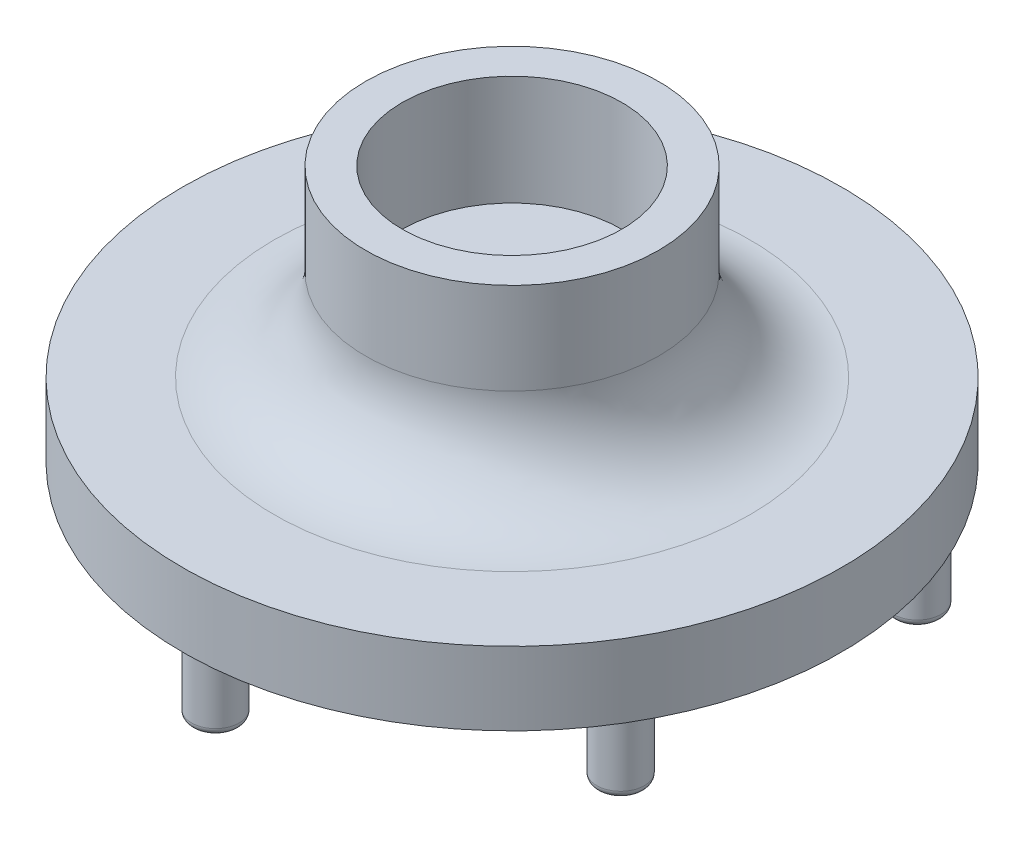
SolidWorks part; units mm, degrees
ref_plane "Front Plane" through (0, 0, 0) normal (0, 0, 1) x (1, 0, 0)
ref_plane "Top Plane" through (0, 0, 0) normal (0, 1, 0) x (1, 0, 0)
ref_plane "Right Plane" through (0, 0, 0) normal (1, 0, 0) x (0, 0, -1)
sketch "Sketch1" plane through (0, 0, 0) normal (0, 0, 1) x (1, 0, 0)
  line L0 (0, 0) -> (-30, 0)
  line L1 (-30, 0) -> (-30, 30)
  line L2 (-30, 30) -> (-50, 30)
  line L3 (-50, 30) -> (-50, 35)
  line L4 (-50, 35) -> (-90, 35)
  line L5 (-90, 35) -> (-90, 55)
  line L6 (-90, 55) -> (-40, 55)
  line L7 (-40, 55) -> (-40, 105)
  line L8 (-40, 105) -> (-30, 105)
  line L9 (-30, 105) -> (-30, 75)
  line L10 (-30, 75) -> (0, 75)
  line L11 (0, 75) -> (0, 0)
  dimension "D1" = 30
  dimension "D2" = 30
  dimension "D3" = 20
  dimension "D4" = 40
  dimension "D5" = 50
  dimension "D6" = 50
  dimension "D7" = 10
  dimension "D8" = 30
  dimension "D9" = 75
  dimension "D10" = 30
revolve "Revolve1" add sketch "Sketch1" angle 360 about L11 region at (-31.4198, 44.8457, 0)
sketch "Sketch2" plane through (0, 55, 0) normal (0, 1, 0) x (1, 0, 0)
  circle A0 centre (0, 81) radius 6.5
  dimension "D1" = 13
  dimension "D2" = 81
extrude "Boss-Extrude1" add sketch "Sketch2" against normal blind 40
pattern_circular "CirPattern1" count 6 over 360 about axis through (0, 55, 0) along (0, 1, 0) of "Boss-Extrude1"
fillet "Fillet1" radius 25 2 edges at (-40, 55, 0) (-30, 30, 0)
fillet "Fillet2" radius 15 1 edges at (-30, 0, 0)
fillet "Fillet5" radius 2 6 edges at (66.8981, 15, -46.1292) (73.3981, 15, 34.8708) (6.5, 15, 81) (-66.8981, 15, 46.1292) (-73.3981, 15, -34.8708) (-6.5, 15, -81)
